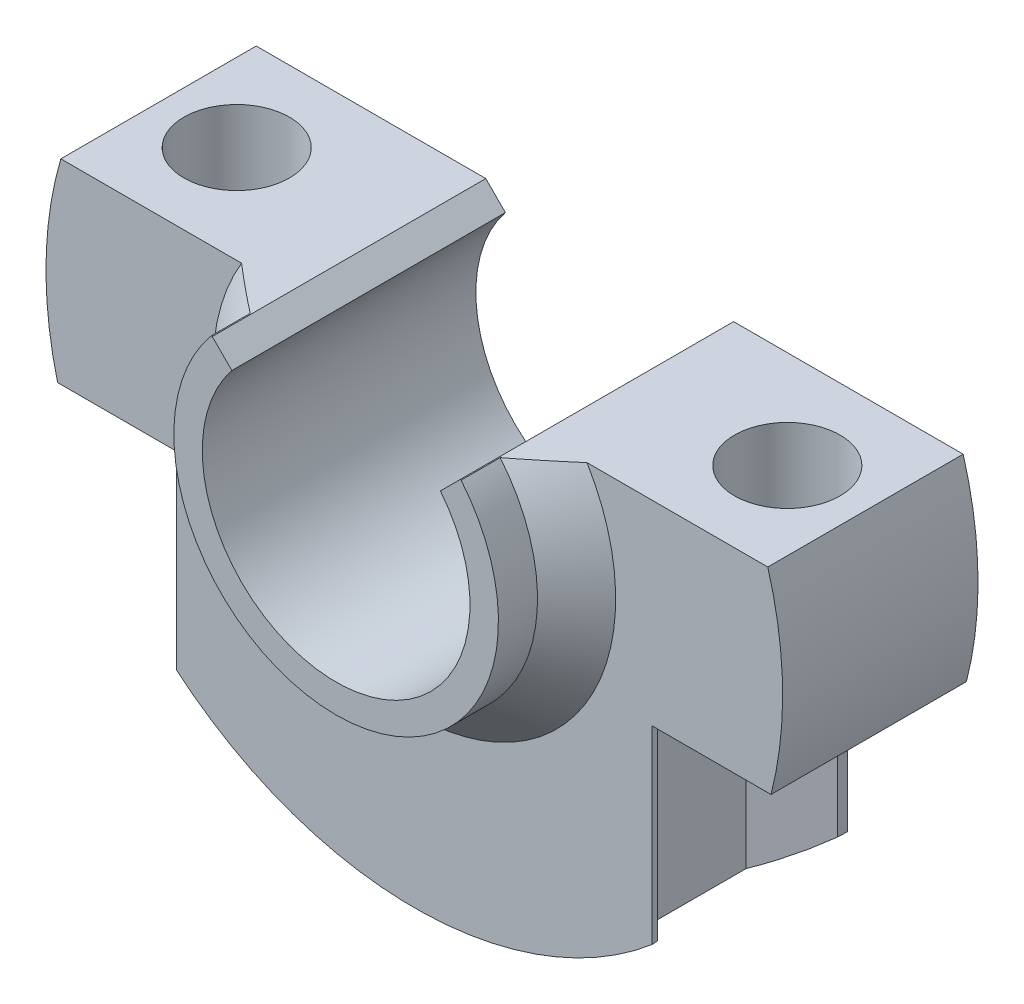
SolidWorks part; units mm, degrees
material "ABS"
ref_plane "Front Plane" through (0, 0, 0) normal (0, 0, 1) x (1, 0, 0)
ref_plane "Top Plane" through (0, 0, 0) normal (0, 1, 0) x (1, 0, 0)
ref_plane "Right Plane" through (0, 0, 0) normal (1, 0, 0) x (0, 0, -1)
sketch "Sketch1" plane through (0, 0, 0) normal (0, 0, 1) x (1, 0, 0)
  line L0 (-1.5875, 2.7496) -> (1.5875, 2.7496) construction
  line L1 (2.1703, 2.6496) -> (9.0449, 2.6496)
  line L2 (-2.1703, 2.6496) -> (-9.0449, 2.6496)
  circle A0 centre (0, 0) radius 3.175 construction
  circle A1 centre (0, 0) radius 3.425
  arc A2 (-9.0449, 2.6496) -> (9.0449, 2.6496) centre (0, 0) ccw
  point P11 (8.232, 1.7931)
  dimension "D1" = 6.35
  dimension "D3" = 0.25
  dimension "D4" = 6
  dimension "D2" = 3.175
  dimension "D5" = 0.1
extrude "Boss-Extrude1" add sketch "Sketch1" along normal mid plane 5 contours L2 A2 L1 A1 region at (5.6076, 2.4258, 0)
sketch "Sketch2" plane through (0, 0, 2.5) normal (0, 0, 1) x (1, 0, 0)
  line L5 (9.0449, 2.6496) -> (2.1703, 2.6496)
  line L8 (-2.1703, 2.6496) -> (-9.0449, 2.6496)
  line L9 (9.0449, 2.6496) -> (2.1703, 2.6496)
  line L12 (-2.1703, 2.6496) -> (-9.0449, 2.6496)
  circle A0 centre (0, 0) radius 4.1529
  arc A3 (-2.1703, 2.6496) -> (2.1703, 2.6496) centre (0, 0) ccw
  arc A4 (-9.0449, 2.6496) -> (9.0449, 2.6496) centre (0, 0) ccw
  arc A5 (-2.1703, 2.6496) -> (2.1703, 2.6496) centre (0, 0) ccw
  arc A6 (-9.0449, 2.6496) -> (9.0449, 2.6496) centre (0, 0) ccw
  point P3 (0, -0.1127)
  arc M10 (2.1703, 2.6496) -> (-2.1703, 2.6496) centre (0, 0) cw
  line M12 (-2.1703, 2.6496) -> (-9.0449, 2.6496)
  dimension "D1" = 8.3058
  dimension "D2" = 0
extrude "Boss-Extrude2" add sketch "Sketch2" along normal blind 2 contours A0 L9 M12 M10 region at (3.8058, 1.3718, 2.5)
chamfer "Chamfer1" distance 1 angle 45 1 edges at (-2.1703, 2.6496, 1) first distance on face at (-4.8043, 2.6496, 1.5)
chamfer "Chamfer2" distance 1 angle 45 1 edges at (2.1703, 2.6496, 1) first distance on face at (4.8043, 2.6496, 1.5)
sketch "Sketch3" plane through (0, 2.6496, 0) normal (0, 1, 0) x (1, 0, 0)
  line L0 (-9.0449, -2.5) -> (-9.0449, 2.5) construction
  line L1 (9.0449, -2.5) -> (9.0449, 2.5) construction
  point P0 (-7.0449, 0)
  point P1 (7.0449, 0)
  point P6 (0, 0)
  dimension "D1" = 2
  dimension "D2" = 2
hole_wizard "M2.5 Clearance Hole1" positions "Sketch3" profile "Sketch4" hole size "M2.5" standard "ANSI Metric" end condition through all
sketch "Sketch4" plane through (-7.0449, 2.6496, 0) normal (1, 0, 0) x (0, 0, 1)
  line L0 (0, 0) -> (0, 12.0746)
  line L1 (0, 12.0746) -> (1.35, 12.0746)
  line L2 (1.35, 12.0746) -> (1.35, 0)
  line L5 (1.35, 0) -> (0, 0)
  line L11 (0, -6.35) -> (0, 107.95) construction
  dimension "Thru Hole Dia." = 2.7
  dimension "Thru Hole Depth" = 12.0746
ref_plane "Plane1" through (0, -9.425, 0) normal (0, -1, 0) x (-1, 0, 0)
sketch "Sketch5" plane through (0, -9.425, 0) normal (0, -1, 0) x (-1, 0, 0)
  line L0 (7.0449, 2.8868) -> (12.0449, 2.8868)
  line L1 (-9.5449, 1.4434) -> (-9.5449, -1.4434)
  line L2 (-9.5449, -1.4434) -> (-7.0449, -2.8868)
  line L3 (-7.0449, -2.8868) -> (-4.5449, -1.4434)
  line L4 (-4.5449, -1.4434) -> (-4.5449, 1.4434)
  line L5 (-4.5449, 1.4434) -> (-7.0449, 2.8868)
  line L6 (-7.0449, 2.8868) -> (-9.5449, 1.4434)
  line L7 (9.5449, -1.4434) -> (9.5449, 1.4434)
  line L8 (9.5449, 1.4434) -> (7.0449, 2.8868)
  line L9 (7.0449, 2.8868) -> (4.5449, 1.4434)
  line L10 (4.5449, 1.4434) -> (4.5449, -1.4434)
  line L11 (4.5449, -1.4434) -> (7.0449, -2.8868)
  line L12 (7.0449, -2.8868) -> (9.5449, -1.4434)
  line L13 (12.0449, 2.8868) -> (12.0449, -2.8868)
  line L14 (12.0449, -2.8868) -> (7.0449, -2.8868)
  line L15 (-7.0449, 2.8868) -> (-12.0449, 2.8868)
  line L16 (-12.0449, 2.8868) -> (-12.0449, -2.8868)
  line L17 (-12.0449, -2.8868) -> (-7.0449, -2.8868)
  circle A0 centre (-7.0449, 0) radius 2.5 construction
  circle A1 centre (7.0449, 0) radius 2.5 construction
  dimension "D1" = 5
  dimension "D2" = 5
extrude "Cut-Extrude1" cut sketch "Sketch5" against normal offset from surface (7.0746 mm away) 5 contours L16 L17 L2 L1 L6 L15 | L5 L6 L1 L2 L3 L4 | L11 L12 L7 L8 L9 L10 | L14 L13 L0 L8 L7 L12 region at (-10.3782, -9.425, 0) region at (-7.0449, -9.425, 0) region at (7.0449, -9.425, 0) region at (10.3782, -9.425, 0) up to face at (-7.0449, 2.6496, 1.35)
chamfer "Chamfer3" distance 0.4 angle 45 2 edges at (6.375, -4.6461, 2.5) (-6.375, -4.6461, 2.5) first distance on face at (5.4698, -4.9886, 1.9774) first distance on face at (-5.4698, -4.9886, 1.9774)
chamfer "Chamfer4" distance 0.4 angle 45 2 edges at (6.375, -4.6461, -2.5) (-6.375, -4.6461, -2.5) first distance on face at (5.4698, -4.9886, -1.9774) first distance on face at (-5.4698, -4.9886, -1.9774)
chamfer "Chamfer5" distance 1 angle 45 1 edges at (0, -4.1529, 2.5)
equation "\"D2@Sketch3\"=\"D1@Sketch3\""
